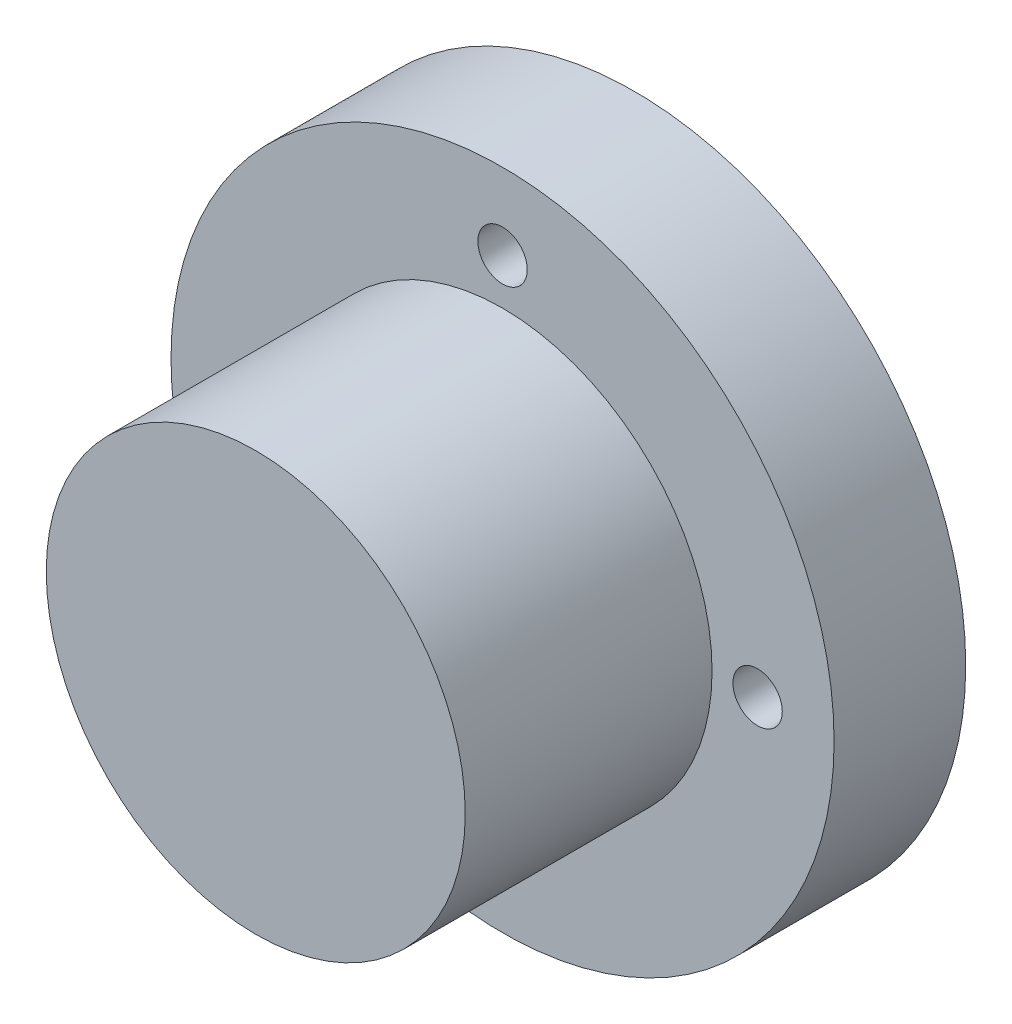
SolidWorks part; units mm, degrees
ref_plane "Front Plane" through (0, 0, 0) normal (0, 0, 1) x (1, 0, 0)
ref_plane "Top Plane" through (0, 0, 0) normal (0, 1, 0) x (1, 0, 0)
ref_plane "Right Plane" through (0, 0, 0) normal (1, 0, 0) x (0, 0, -1)
sketch "Sketch1" plane through (0, 0, 0) normal (0, 0, 1) x (1, 0, 0)
  circle A0 centre (0, 0) radius 15.5
  circle A1 centre (0, 15.5) radius 1.5
  circle A2 centre (15.5, 0) radius 1.5
  circle A3 centre (0, -15.5) radius 1.5
  circle A4 centre (-15.5, 0) radius 1.5
  circle A5 centre (0, 0) radius 20.15
  dimension "D1" = 31
  dimension "D2" = 3
  dimension "D3" = 40.3
extrude "Boss-Extrude1" add sketch "Sketch1" along normal blind 8 contours A5 A4 A0 A1 A2 A3 | A4 A0 A3 A2 A1 region at (0, 0, 0) region at (-19.5801, 0, 0)
sketch "Sketch2" plane through (0, 0, 8) normal (0, 0, 1) x (1, 0, 0)
  circle A0 centre (0, 0) radius 12.7324
  dimension "D1" = 25.4648
extrude "Boss-Extrude2" add sketch "Sketch2" along normal blind 15
equation "\"D3@Sketch1\"=20.15*2"
equation "\"TEETH\"= 16"
equation "\"PITCH\"= 5mm"
equation "\"C\"= \"TEETH\" * \"PITCH\""
equation "\"RADIUS\"= \"C\" / ( 2 * PI )"
equation "\"D1@Sketch2\"=\"RADIUS\"*2"
